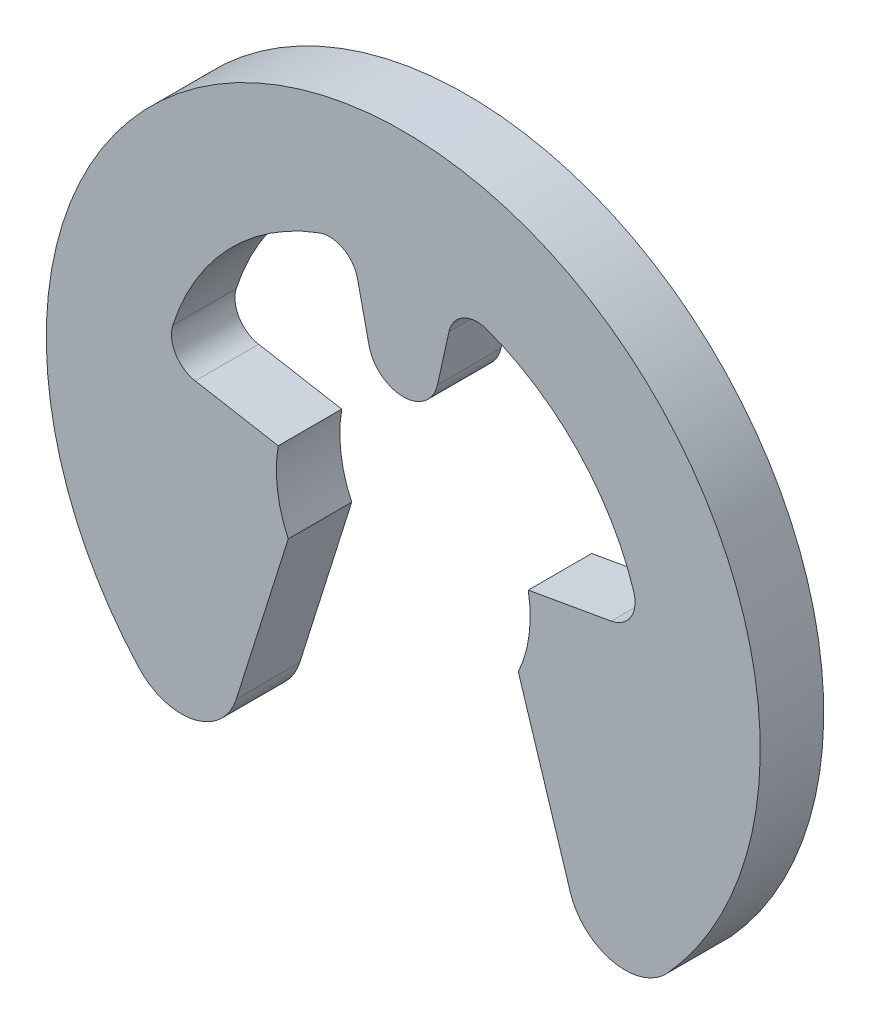
SolidWorks part; units mm, degrees
ref_plane "Plane1" through (0, 0, 0) normal (0, 0, 1) x (1, 0, 0)
ref_plane "Plane2" through (0, 0, 0) normal (0, 1, 0) x (1, 0, 0)
ref_plane "Plane3" through (0, 0, 0) normal (1, 0, 0) x (0, 0, -1)
sketch "BodySke" plane through (0, 0, 0) normal (0, 0, 1) x (1, 0, 0)
  line L0 (-0.7581, 0) -> (0.7581, 0) construction
  line L1 (0, 0) -> (0, 1.125) construction
  line L2 (0, 0) -> (0.1641, 0.7402) construction
  line L3 (0, 0) -> (1.0196, -0.4754) construction
  line L4 (0, 0) -> (-0.1641, 0.7402) construction
  line L5 (0, 0) -> (-1.0196, -0.4754) construction
  line L6 (0.3939, 0.0695) -> (0.6556, 0.1156)
  line L7 (-0.3939, 0.0695) -> (-0.6556, 0.1156)
  line L8 (0, 0) -> (1.1079, 0.1954) construction
  line L9 (0.3625, -0.169) -> (0.5263, -0.6884)
  line L10 (-0.3625, -0.169) -> (-0.5263, -0.6884)
  line L11 (0.1079, 0.4866) -> (0.1441, 0.65)
  line L12 (-0.1079, 0.4866) -> (-0.1441, 0.65)
  line L13 (0, 0) -> (-1.1079, 0.1954) construction
  circle A0 centre (0, 0) radius 0.4 construction
  arc A1 (0.7262, 0.2325) -> (0.2639, 0.7154) centre (0, 0) ccw
  arc A2 (0.8334, -0.7557) -> (-0.8334, -0.7557) centre (0, 0) ccw
  arc A3 (0.3625, -0.169) -> (0.3939, 0.0695) centre (0, 0) ccw
  arc A4 (-0.2639, 0.7154) -> (-0.7262, 0.2325) centre (0, 0) ccw
  arc A5 (0.6556, 0.1156) -> (0.7262, 0.2325) centre (0.6399, 0.2049) ccw
  arc A7 (0.2639, 0.7154) -> (0.1441, 0.65) centre (0.2326, 0.6303) ccw
  arc A8 (-0.3939, 0.0695) -> (-0.3625, -0.169) centre (0, 0) ccw
  arc A9 (-0.7262, 0.2325) -> (-0.6556, 0.1156) centre (-0.6399, 0.2049) ccw
  arc A10 (-0.1079, 0.4866) -> (0.1079, 0.4866) centre (0, 0.5105) ccw
  arc A11 (-0.1441, 0.65) -> (-0.2639, 0.7154) centre (-0.2326, 0.6303) ccw
  arc A12 (-0.8334, -0.7557) -> (-0.5263, -0.6884) centre (-0.6991, -0.6339) ccw
  arc A13 (0.5263, -0.6884) -> (0.8334, -0.7557) centre (0.6991, -0.6339) ccw
  dimension "TipRad" = 0.1812
  dimension "CavityFilletRad" = 0.0906
  dimension "GrooveDia" = 0.8
  dimension "D3" = 25
  dimension "D4" = 35
  dimension "D1" = 35
  dimension "D2" = 160
extrude "Body" add sketch "BodySke" against normal blind 0.2
equation "' \"Thickness@Body\" = 0.2"
equation "' \"GrooveDia@BodySke\" = 0.8"
equation "' \"OutsideDia@BodySke\" = 2.25"
equation "' \"Thickness@Body\" = 2.5"
equation "' \"GrooveDia@BodySke\" = 30"
equation "' \"OutsideDia@BodySke\" = 52.6"
equation "\"CavityDia@BodySke\" = (\"OutsideDia@BodySke\"  + \"GrooveDia@BodySke\") / 2 "
equation "\"CavityFilletRad@BodySke\" =  (\"CavityDia@BodySke\" - \"GrooveDia@BodySke\") / 2 * 0.25"
equation "\"TipRad@BodySke\" = (\"OutsideDia@BodySke\"  - \"GrooveDia@BodySke\") / 2 * 0.25"
